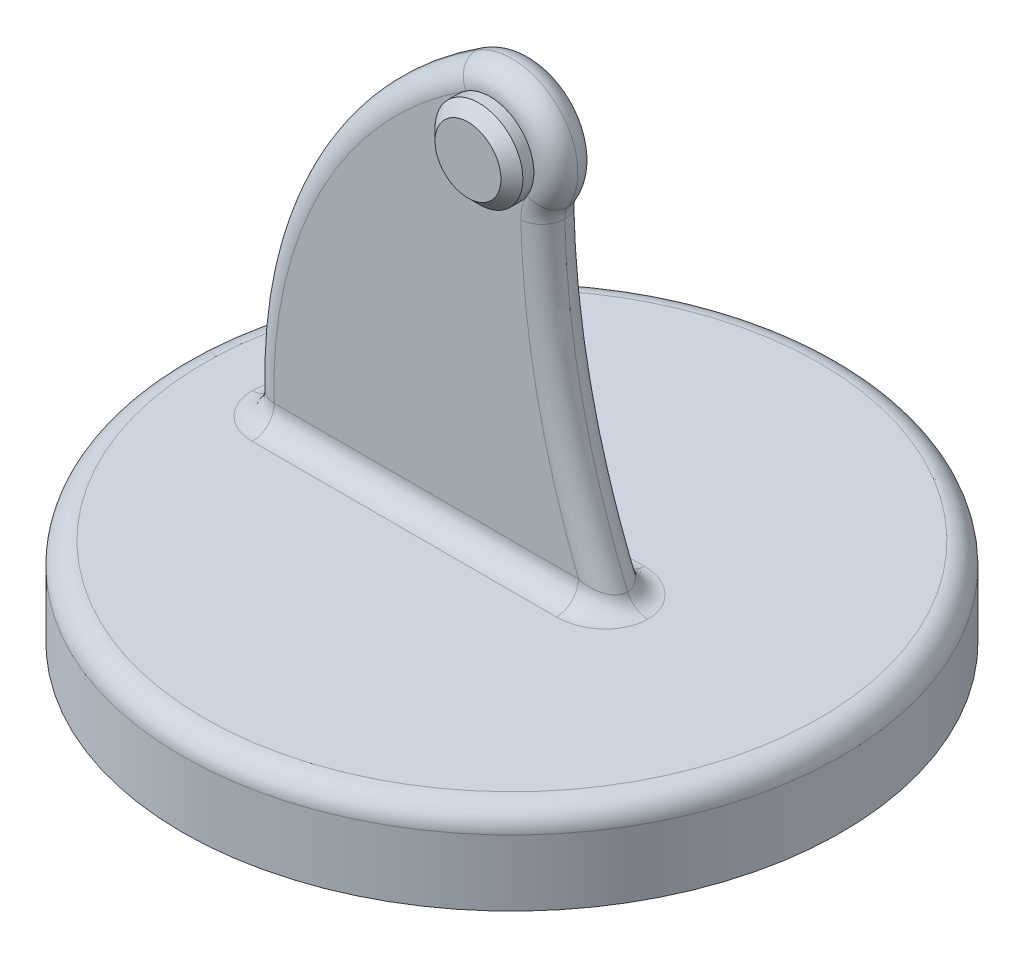
SolidWorks part; units mm, degrees
ref_plane "Front Plane" through (0, 0, 0) normal (0, 0, 1) x (1, 0, 0)
ref_plane "Top Plane" through (0, 0, 0) normal (0, 1, 0) x (1, 0, 0)
ref_plane "Right Plane" through (0, 0, 0) normal (1, 0, 0) x (0, 0, -1)
sketch "Sketch1" plane through (0, 0, 0) normal (0, 1, 0) x (1, 0, 0)
  circle A0 centre (0, 0) radius 75
  dimension "D1" = 150
extrude "Boss-Extrude1" add sketch "Sketch1" along normal blind 20
fillet "Fillet1" radius 5 1 edges at (0, 20, 75)
sketch "Sketch2" plane through (0, 0, 0) normal (0, 0, 1) x (1, 0, 0)
  line L0 (0, 0) -> (0, 100) construction
  line L1 (-75, 15) -> (75, 15) construction
  line L2 (-53.2385, 15) -> (30, 15)
  circle A0 centre (0, 100) radius 15
  arc A1 (-8.0922, 112.63) -> (-53.2385, 15) centre (45.8556, 28.43) ccw
  arc A2 (30, 15) -> (11.9902, 90.9869) centre (191.9724, 93.5172) cw
  dimension "D4" = 30
  dimension "D5" = 100
  dimension "D6" = 180
  dimension "D1" = 30
  dimension "D3" = 100
extrude "Boss-Extrude2" add sketch "Sketch2" along normal mid plane 10
fillet "Fillet2" radius 5 8 edges at (-13.0591, 20, 5) (-13.0591, 20, -5) (-43.8254, 72.6715, 5) (-43.8254, 72.6715, -5) (10.9957, 110.2027, -5) (10.9957, 110.2027, 5) (16.2091, 54.6936, 5) (16.2091, 54.6936, -5)
sketch "Sketch3" plane through (0, 0, 5) normal (0, 0, 1) x (1, 0, 0)
  circle A0 centre (0, 100) radius 10
  dimension "D1" = 20
extrude "Boss-Extrude3" add sketch "Sketch3" along normal blind 5
chamfer "Chamfer1" distance 2.5 angle 45 1 edges at (10, 100, 10)
sketch "Sketch4" plane through (0, 0, -5) normal (0, 0, -1) x (-1, 0, 0)
  circle A0 centre (0, 100) radius 10
  dimension "D1" = 20
extrude "Cut-Extrude1" cut sketch "Sketch4" against normal blind 10
